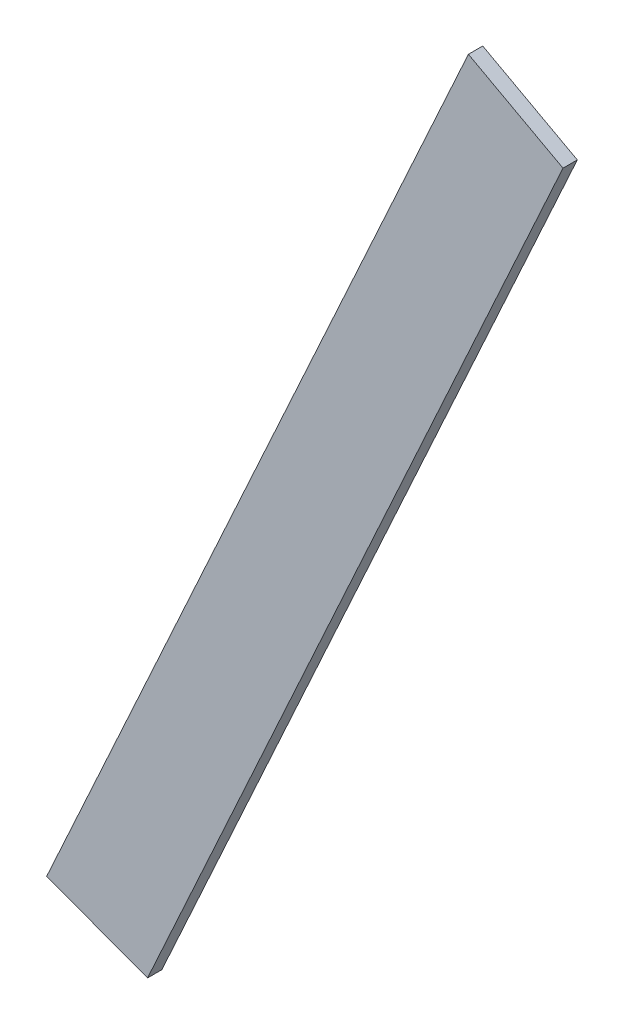
SolidWorks part; units mm, degrees
ref_plane "Front Plane" through (0, 0, 0) normal (0, 0, 1) x (1, 0, 0)
ref_plane "Top Plane" through (0, 0, 0) normal (0, 1, 0) x (1, 0, 0)
ref_plane "Right Plane" through (0, 0, 0) normal (1, 0, 0) x (0, 0, -1)
sketch "Sketch1" plane through (0, 0, 0) normal (0, 0, 1) x (1, 0, 0)
  line L0 (31.5533, -12.4331) -> (17.4675, -7.1674)
  line L2 (17.4675, -7.1674) -> (76.3905, 121.7569)
  line L4 (31.5533, -12.4331) -> (89.6043, 114.5833)
  line L5 (89.6043, 114.5833) -> (76.3905, 121.7569)
  line L6 (149.6851, 81.966) -> (-26.0832, 177.3889) construction
  line L7 (-91.6004, 33.6052) -> (95.7375, -36.4269) construction
  dimension "D1" = 15
extrude "Boss-Extrude1" add sketch "Sketch1" along normal blind 2
ref_plane "Plane1" through (23.9804, -10.9599, 0) normal (0.9095, -0.4157, 0) x (0, 0, -1)
